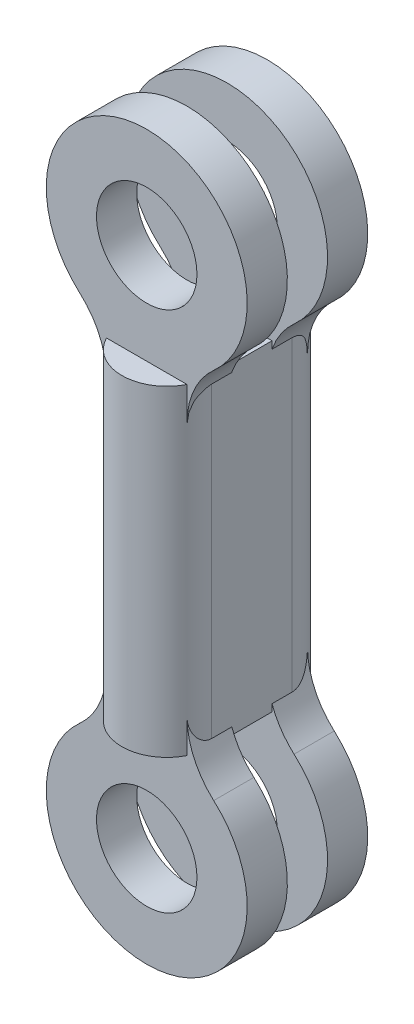
SolidWorks part; units mm, degrees
ref_plane "Front Plane" through (0, 0, 0) normal (0, 0, 1) x (1, 0, 0)
ref_plane "Top Plane" through (0, 0, 0) normal (0, 1, 0) x (1, 0, 0)
ref_plane "Right Plane" through (0, 0, 0) normal (1, 0, 0) x (0, 0, -1)
sketch "Sketch1" plane through (0, 0, 0) normal (0, 0, 1) x (1, 0, 0)
  line L0 (32.9763, 32.5) -> (-31.8549, 32.5) construction
  line L1 (5, 18.4564) -> (-5, 18.4564)
  line L2 (5, 18.4564) -> (5, 16.7705)
  line L4 (-5, 18.4564) -> (-5, 16.7705)
  line L5 (-5, 46.5436) -> (-5, 48.2295)
  line L6 (5, 46.5436) -> (5, 48.2295)
  line L7 (5, 46.5436) -> (-5, 46.5436)
  arc A0 (-8.3333, 9.3169) -> (8.3333, 9.3169) centre (0, 0) ccw
  circle A1 centre (0, 0) radius 6.25
  arc A2 (8.3333, 55.6831) -> (5, 48.2295) centre (15, 48.2295) ccw
  arc A3 (-5, 16.7705) -> (-8.3333, 9.3169) centre (-15, 16.7705) cw
  arc A4 (8.3333, 9.3169) -> (5, 16.7705) centre (15, 16.7705) cw
  arc A5 (-5, 48.2295) -> (-8.3333, 55.6831) centre (-15, 48.2295) ccw
  circle A6 centre (0, 65) radius 6.25
  arc A7 (-8.3333, 55.6831) -> (8.3333, 55.6831) centre (0, 65) cw
  point P1 (0, 18.4564)
  point P4 (0, 12.7784)
  point P5 (0, 32.5)
  point P16 (5, 11.4564)
  point P27 (5, 53.5436)
  point P28 (0, 52.2216)
  dimension "D1" = 25
  dimension "D2" = 12.5
  dimension "D5" = 10
  dimension "D3" = 10
  dimension "D4" = 7
  dimension "32.5" = 32.5
extrude "Boss-Extrude1" add sketch "Sketch1" along normal blind 5 from offset 2.5 contours A6 | A0 A4 L2 L1 L4 A3 A1 | A2 L6 L7 L5 A5 A7 region at (4.6021, 17.6135, 0) region at (0, 65, 0)
extrude "Boss-Extrude2" add sketch "Sketch1<2>" against normal blind 5 from offset 2.5 separate body contours L4 A0 L2 L1 A1 | A2 L6 L7 L5 A5 A7 | A6 region at (4.6021, 17.6135, 0) offset against normal yes
sketch "Sketch1<2>" plane through (0, 0, 0) normal (0, 0, 1) x (1, 0, 0) same geometry as "Sketch1"
sketch "Sketch2" plane through (0, 0, 0) normal (0, 1, 0) x (1, 0, 0)
  line L0 (0, 5) -> (0, -5) construction
  line L1 (5.5902, 5) -> (5.5902, -5)
  line L2 (-5.5902, 5) -> (-5.5902, -5)
  arc A0 (5.5902, 5) -> (-5.5902, 5) centre (0, 5) ccw
  arc A1 (-5.5902, -5) -> (5.5902, -5) centre (0, -5) ccw
  point P2 (0, 0)
  dimension "D2" = 10
extrude "Boss-Extrude3" add sketch "Sketch2" along normal blind 40 from offset 12.5
sketch "Sketch3" plane through (0, 12.5, 0) normal (0, -1, 0) x (1, 0, 0)
  line L0 (-5.5902, 0) -> (5.5902, 0) construction
  line L1 (-5.5902, -2.5) -> (-5.5902, 2.5) construction
  line L2 (5.5902, 2.5) -> (5.5902, -2.5) construction
  line L3 (0, 2.5) -> (0, -2.5) construction
  line L4 (5.5902, 2.5) -> (-5.5902, 2.5) construction
  line L5 (12.5, -2.5) -> (-12.5, -2.5) construction
  circle A0 centre (0, 0) radius 1.5
  dimension "D1" = 3
  dimension "D2" = 0
extrude "Cut-Extrude1" cut sketch "Sketch3" against normal blind 64
